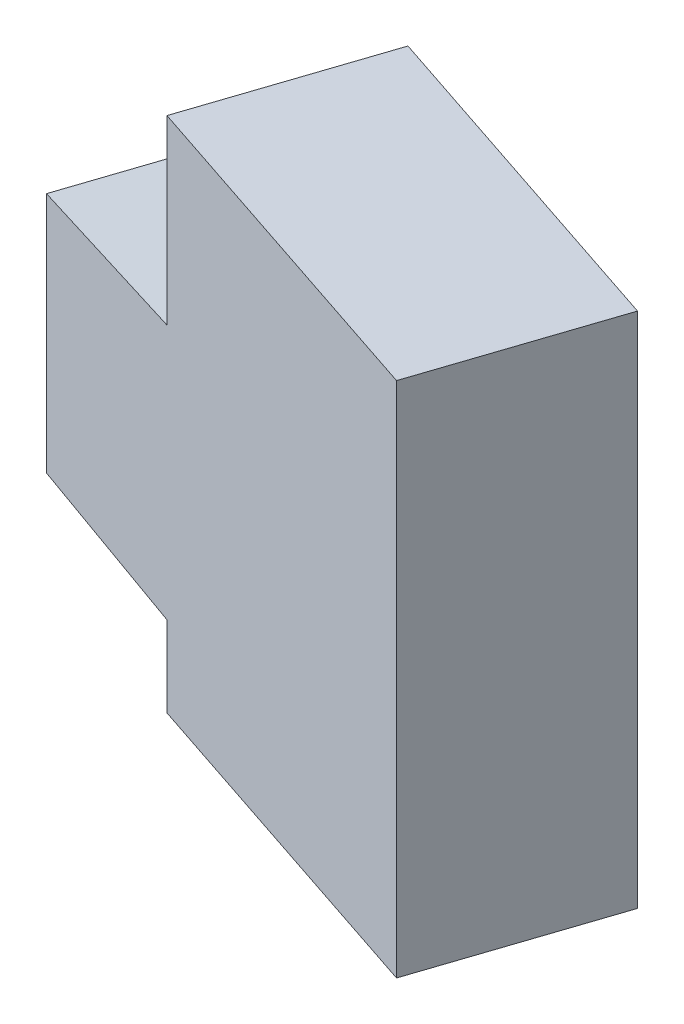
SolidWorks part; units mm, degrees
ref_plane "Front Plane" through (0, 0, 0) normal (0, 0, 1) x (1, 0, 0)
ref_plane "Top Plane" through (0, 0, 0) normal (0, 1, 0) x (1, 0, 0)
ref_plane "Right Plane" through (0, 0, 0) normal (1, 0, 0) x (0, 0, -1)
ref_axis "Axis1" through (-48.2288, 228.6, 5.0904) along (-0.9487, 0, -0.3162)
ref_plane "Plane1" through (-6.35, 0, 19.05) normal (-0.3162, 0, 0.9487) x (0.9487, 0, 0.3162)
sketch "Sketch1" plane through (-6.35, 0, 19.05) normal (-0.3162, 0, 0.9487) x (0.9487, 0, 0.3162)
  line L0 (-45.2414, 218.569) -> (-45.2414, 178.1018) construction
  line L1 (-45.2414, 218.569) -> (-45.2414, 178.1018) construction
  line L2 (-45.2414, 226.7712) -> (-45.2414, 230.4288) construction
  line L3 (-45.2414, 226.7712) -> (-45.2414, 230.4288) construction
  line L4 (-45.2414, 223.5962) -> (-33.8114, 223.5962)
  line L5 (-33.8114, 223.5962) -> (-33.8114, 207.3022)
  line L6 (-33.8114, 207.3022) -> (-45.2414, 207.3022)
  line L7 (-45.2414, 207.3022) -> (-45.2414, 209.8422)
  line L8 (-45.2414, 209.8422) -> (-51.2414, 210.0517)
  line L9 (-51.2414, 210.0517) -> (-51.2414, 217.6717)
  line L13 (-45.2414, 220.4212) -> (-45.2414, 223.5962)
  line L18 (-51.2414, 218.569) -> (-51.2414, 178.1018) construction
  line L19 (-51.2414, 217.6717) -> (-45.2414, 217.8812)
  line L20 (-45.2414, 217.8812) -> (-45.2414, 220.4212)
  dimension "D1" = 11.43
  dimension "D3" = 3.175
  dimension "D4" = 7.62
  dimension "D5" = 2.54
  dimension "D6" = 3.175
  dimension "D7" = 92
extrude "Boss-Extrude1" add sketch "Sketch1" along normal mid plane 6
